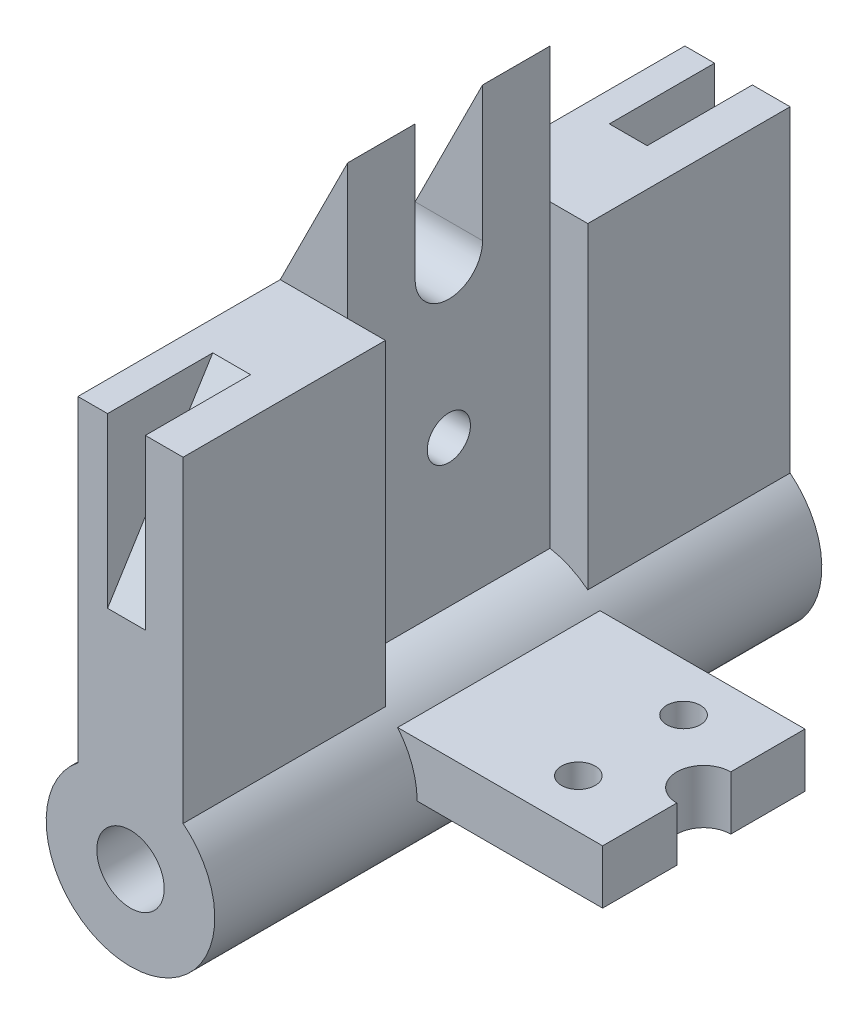
SolidWorks part; units mm, degrees
ref_plane "Front Plane" through (0, 0, 0) normal (0, 0, 1) x (1, 0, 0)
ref_plane "Top Plane" through (0, 0, 0) normal (0, 1, 0) x (1, 0, 0)
ref_plane "Right Plane" through (0, 0, 0) normal (1, 0, 0) x (0, 0, -1)
sketch "Sketch1" plane through (0, 0, 0) normal (0, 0, 1) x (1, 0, 0)
  line L0 (15.875, 0) -> (50.8, 0)
  line L1 (50.8, 0) -> (50.8, 10.16)
  line L2 (50.8, 10.16) -> (12.198, 10.16)
  line L3 (0, 15.875) -> (0, 72.136) construction
  line L4 (-9.906, 12.4051) -> (-9.906, 72.136)
  line L5 (9.906, 12.4051) -> (9.906, 72.136)
  line L6 (-9.906, 72.136) -> (9.906, 72.136)
  line L7 (2.794, 72.136) -> (2.794, 15.6272)
  line L8 (2.794, 72.136) -> (2.794, 97.536)
  line L9 (2.794, 97.536) -> (-9.906, 72.136)
  circle A0 centre (0, 0) radius 15.875
  circle A1 centre (0, 0) radius 6.35
  dimension "D1" = 31.75
  dimension "D2" = 12.7
  dimension "D3" = 10.16
  dimension "D4" = 50.8
  dimension "D5" = 9.906
  dimension "D6" = 9.906
  dimension "D7" = 72.136
  dimension "D8" = 12.7
  dimension "D9" = 25.4
extrude "Boss-Extrude1" add sketch "Sketch1" along normal mid plane 38.1 contours L8 L9 L6 | A0 L3 L6 L4 | L3 A0 L7 L6 | A0 A1 | A0 L0 L1 L2 region at (32.7402, 5.1638, 0) region at (-6.6885, -13.9005, 0) region at (-5.0016, 43.4461, 0) region at (-1.4393, 80.6027, 0) region at (1.398, 43.9643, 0)
extrude "Boss-Extrude2" add sketch "Sketch1<3>" along normal blind 38.1 from vertex contours A0 L3 L6 L4 | A0 A1 | A0 L5 L6 L7 | L3 A0 L7 L6 region at (-6.6885, -13.9005, 0) region at (-5.0016, 43.4461, 0) region at (6.3826, 43.2475, 0) region at (1.398, 43.9643, 0) starting at point (2.794, 97.536, 19.05)
sketch "Sketch1<3>" plane through (0, 0, 0) normal (0, 0, 1) x (1, 0, 0) same geometry as "Sketch1"
extrude "Boss-Extrude3" add sketch "Sketch1<4>" against normal blind 38.1 from vertex contours A0 L5 L6 L7 | A0 L3 L6 L4 | A0 A1 | L3 A0 L7 L6 region at (-6.6885, -13.9005, 0) region at (-5.0016, 43.4461, 0) region at (6.3826, 43.2475, 0) region at (1.398, 43.9643, 0) starting at point (2.794, 97.536, -19.05)
sketch "Sketch1<4>" plane through (0, 0, 0) normal (0, 0, 1) x (1, 0, 0) same geometry as "Sketch1"
sketch "Sketch2" plane through (0, 72.136, 0) normal (0, 1, 0) x (1, 0, 0)
  line L0 (-4.318, -57.15) -> (-4.318, -37.338)
  line L1 (-9.906, -57.15) -> (9.906, -57.15) construction
  line L2 (-4.318, -37.338) -> (2.794, -37.338)
  line L3 (2.794, -37.338) -> (2.794, -57.15)
  line L4 (-9.906, -57.15) -> (-9.906, -19.05) construction
  line L5 (9.906, -57.15) -> (9.906, -19.05) construction
  line L11 (-4.318, -57.15) -> (2.794, -57.15)
  dimension "D1" = 5.588
  dimension "D2" = 7.112
  dimension "D3" = 19.812
sketch "Sketch3" plane through (9.906, 0, 0) normal (1, 0, 0) x (0, 0, -1)
  line L0 (-37.338, 72.136) -> (-57.15, 40.386)
  line L1 (-57.15, 72.136) -> (-19.05, 72.136) construction
  line L2 (-57.15, 12.4051) -> (-57.15, 72.136) construction
  dimension "D1" = 19.812
  dimension "D2" = 31.75
extrude "Cut-Extrude1" cut sketch "Sketch2" along direction (0, -0.8484, 0.5294) on the side against the normal through all
mirror "Mirror1" about plane through (0, 0, 0) normal (0, 0, 1) of "Cut-Extrude1"
sketch "Sketch4" plane through (2.794, 0, 0) normal (1, 0, 0) x (0, 0, -1)
  line L0 (0, 97.536) -> (0, 72.136) construction
  line L1 (-19.05, 97.536) -> (19.05, 97.536) construction
  line L2 (-6.35, 72.136) -> (-6.35, 97.536)
  line L3 (6.35, 72.136) -> (6.35, 97.536)
  line L4 (0, 43.18) -> (0, 72.136) construction
  circle A0 centre (0, 72.136) radius 6.35
  circle A1 centre (0, 43.18) radius 4.064
  line M4 (19.05, 97.536) -> (-19.05, 97.536)
  dimension "D3" = 8.128
  dimension "D1" = 25.4
  dimension "D2" = 12.7
  dimension "D4" = 28.956
extrude "Cut-Extrude2" cut sketch "Sketch4" against normal through all contours A0 L3 L2 M4 | A0 | A1 region at (2.794, 87.2804, 0) region at (2.794, 72.136, 0) region at (2.794, 43.18, 0)
sketch "Sketch5" plane through (0, 10.16, 0) normal (0, 1, 0) x (1, 0, 0)
  line L0 (50.8, -19.05) -> (50.8, 19.05) construction
  line L1 (50.8, -19.05) -> (12.198, -19.05) construction
  circle A0 centre (37.084, -9.906) radius 3.175
  circle A1 centre (37.084, 9.906) radius 3.175
  circle A2 centre (50.8, 0) radius 5.08
  dimension "D1" = 6.35
  dimension "D5" = 10.16
  dimension "D2" = 13.716
  dimension "D3" = 19.812
  dimension "D4" = 9.144
extrude "Cut-Extrude3" cut sketch "Sketch5" against normal through all
